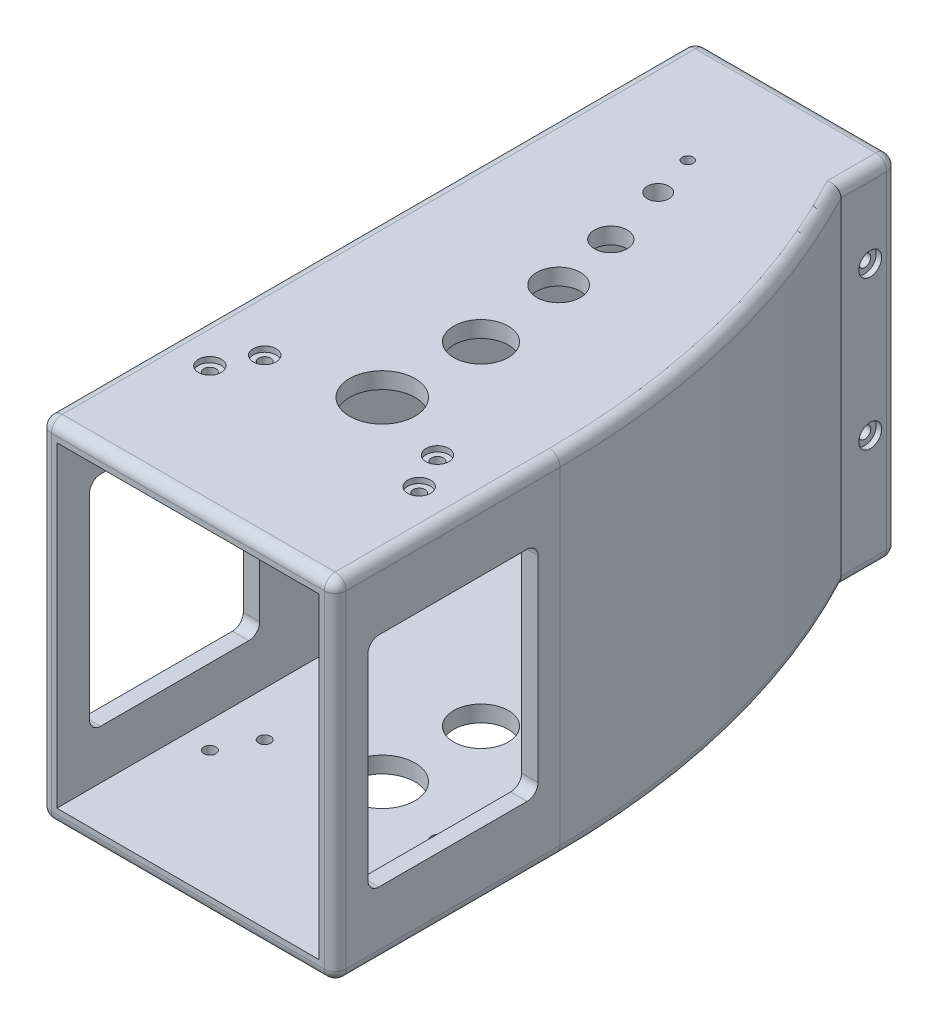
SolidWorks part; units mm, degrees
material "Custom Plastic"
ref_plane "Front Plane" through (0, 0, 0) normal (0, 0, 1) x (1, 0, 0)
ref_plane "Top Plane" through (0, 0, 0) normal (0, 1, 0) x (1, 0, 0)
ref_plane "Right Plane" through (0, 0, 0) normal (1, 0, 0) x (0, 0, -1)
sketch "Sketch3" plane through (0, 0, 0) normal (0, 1, 0) x (1, 0, 0)
  line L0 (0, 0) -> (54, 0)
  line L1 (54, 0) -> (54, 41.2013)
  line L2 (31, 120) -> (0, 120)
  line L3 (0, 120) -> (0, 0)
  arc A0 (54, 41.2013) -> (31, 120) centre (-92.4833, 41.2013) ccw
  dimension "D1" = 54
  dimension "D2" = 31
  dimension "D3" = 120
extrude "Boss-Extrude1" add sketch "Sketch3" along normal blind 64
sketch "Sketch5" plane through (0, 64, 0) normal (0, 1, 0) x (1, 0, 0)
  line L0 (31, 120) -> (37.0293, 120)
  line L1 (37.0293, 120) -> (37.0293, 109.64)
  arc A0 (54, 41.2013) -> (31, 120) centre (-92.4833, 41.2013) ccw construction
  arc A1 (31, 120) -> (37.0293, 109.64) centre (31, 113.0656) ccw
extrude "Boss-Extrude2" add sketch "Sketch5" against normal up to surface (64 mm away) up to face at (28.9265, 0, -56.5691)
shell "Shell1" thickness 3 removed face at (27, 32, 0)
fillet "Fillet1" radius 2 8 edges at (49.694, 0, -76.457) (49.694, 64, -76.457) (18.5146, 0, -120) (18.5146, 64, -120) (54, 0, -20.6007) (54, 64, -20.6007) (0, 0, -60) (0, 64, -60)
sketch "Sketch6" plane through (0, 0, -120) normal (0, 0, -1) x (-1, 0, 0)
  line L0 (0, 62) -> (-37.0293, 62) construction
  line L1 (-31.9074, 34) -> (-3, 34)
  line L2 (-31.9074, 34) -> (-31.9074, 59)
  line L3 (-31.9074, 59) -> (-3, 59)
  line L4 (-3, 34) -> (-3, 59)
  line L5 (-31.9074, 34) -> (-3, 59) construction
  line L6 (-31.9074, 59) -> (-3, 34) construction
  line L7 (0, 62) -> (0, 2) construction
  point P0 (-17.4537, 46.5)
  dimension "D1" = 3
  dimension "D2" = 3
  dimension "D3" = 25
extrude "Cut-Extrude1" cut sketch "Sketch6" against normal blind 64
sketch "Sketch8" plane through (37.0293, 0, 0) normal (1, 0, 0) x (0, 0, -1)
  line L0 (120, 2) -> (120, 62) construction
  circle A0 centre (115, 48.9095) radius 2.1
  circle A1 centre (115, 21.6579) radius 2.1
  point P6 (0, 0)
  point P7 (0, 0)
  dimension "D1" = 4.2
  dimension "D2" = 4.2
  dimension "D3" = 5
extrude "Cut-Extrude2" cut sketch "Sketch8" against normal blind 1
fillet "Fillet2" radius 2 13 edges at (0.5858, 63.4142, 0) (0, 32, 0) (0.5858, 0.5858, 0) (27, 0, 0) (53.4142, 0.5858, 0) (54, 32, 0) (53.4142, 63.4142, 0) (37.0293, 0, -111.6238) (37.0293, 0.5858, -119.4142) (37.0293, 32, -120) (37.0293, 63.4142, -119.4142) (27, 64, 0) (37.0293, 64, -111.6238)
fillet "Fillet3" radius 2 3 edges at (0.5858, 63.4142, -119.4142) (0.5858, 0.5858, -119.4142) (0, 32, -120)
fillet "Fillet4" radius 2 4 edges at (3, 34, -118.5) (31.9074, 34, -118.5) (31.9074, 59, -118.5) (3, 59, -118.5)
sketch "Sketch9" plane through (37.0293, 0, 0) normal (1, 0, 0) x (0, 0, -1)
  circle A0 centre (115, 48.9095) radius 1.1
  circle A1 centre (115, 21.6579) radius 1.1
  dimension "D1" = 2.2
  dimension "D2" = 2.2
extrude "Cut-Extrude3" cut sketch "Sketch9" against normal through all
sketch "Sketch10" plane through (0, 0, 0) normal (-1, 0, 0) x (0, 0, 1)
  circle A0 centre (-115, 48.9095) radius 2.1
  circle A1 centre (-115, 21.6579) radius 2.1
  dimension "D1" = 4.2
  dimension "D2" = 4.2
extrude "Cut-Extrude4" cut sketch "Sketch10" against normal blind 1
sketch "Sketch12" plane through (0, 64, 0) normal (0, 1, 0) x (1, 0, 0)
  line L0 (27, 2) -> (27, 41.1991) construction
  line L1 (2, 2) -> (52, 2) construction
  circle A0 centre (7.8252, 23.2099) radius 2.1
  circle A1 centre (11.172, 29.9036) radius 2.1
  dimension "D1" = 4.2
  dimension "D2" = 4.2
extrude "Cut-Extrude5" cut sketch "Sketch12" against normal blind 1
sketch "Sketch13" plane through (0, 64, 0) normal (0, 1, 0) x (1, 0, 0)
  circle A0 centre (7.8252, 23.2099) radius 1.1
  circle A1 centre (11.172, 29.9036) radius 1.1
  dimension "D1" = 2.2
  dimension "D2" = 2.2
extrude "Cut-Extrude6" cut sketch "Sketch13" against normal through all
sketch "Sketch14" plane through (0, 64, 0) normal (0, 1, 0) x (1, 0, 0)
  line L0 (27, 2) -> (27, 37.0116) construction
  line L1 (2, 2) -> (52, 2) construction
sketch "Sketch16" plane through (0, 0, -117) normal (0, 0, 1) x (1, 0, 0)
  line L0 (27, 62) -> (27, 14.4836) construction
  line L1 (52, 62) -> (2, 62) construction
ref_plane "Plane1" through (27, 0, 0) normal (-1, 0, 0) x (0, 0, 1)
mirror "Mirror1" about plane through (27, 0, 0) normal (-1, 0, 0) of "Cut-Extrude6", "Cut-Extrude5"
sketch "Sketch17" plane through (0, 0, -117) normal (0, 0, 1) x (1, 0, 0)
  line L0 (34.0293, 32) -> (56.7152, 32) construction
  line L1 (34.0293, 3) -> (34.0293, 61) construction
sketch "Sketch18" plane through (0, 0, 0) normal (0, -1, 0) x (1, 0, 0)
  circle A0 centre (7.8252, -23.2099) radius 2.1
  circle A1 centre (11.172, -29.9036) radius 2.1
  circle A2 centre (42.828, -29.9036) radius 2.1
  circle A3 centre (46.1748, -23.2099) radius 2.1
  dimension "D1" = 4.2
  dimension "D2" = 4.2
  dimension "D3" = 4.2
  dimension "D4" = 4.2
extrude "Cut-Extrude7" cut sketch "Sketch18" against normal blind 1
sketch "Sketch19" plane through (0, 0, 0) normal (-1, 0, 0) x (0, 0, 1)
  line L0 (-2, 32) -> (-118, 32) construction
  line L1 (-2, 2) -> (-2, 62) construction
  line L2 (-118, 62) -> (-118, 2) construction
  text T0 "                            SMART METHODS"
extrude "Cut-Extrude8" cut sketch "Sketch19" against normal blind 0.3
sketch "Sketch21" plane through (0, 64, 0) normal (0, 1, 0) x (1, 0, 0)
  line L0 (28.627, 33.9953) -> (31.2938, 61.488) construction
  line L1 (31.2938, 61.488) -> (18.9803, 99.6147) construction
  circle A0 centre (28.627, 33.9953) radius 6
  circle A1 centre (28.8537, 51.8609) radius 5
  circle A2 centre (26.9382, 67.9921) radius 4
  circle A3 centre (24.4898, 80.0045) radius 3
  circle A4 centre (21.3819, 91.7911) radius 2
  circle A5 centre (18.9803, 99.6147) radius 1
  spline S0 degree 2 poles (28.627, 33.9953) (31.2938, 61.488) (18.9803, 99.6147) knots 0 0 0 1 1 1
  point P13 (22.2451, 95.0241)
  point P14 (26.1873, 82.6345)
  point P15 (23.3715, 93.7101)
  point P16 (22.8083, 92.2083)
  point P17 (24.4978, 80.0064)
  point P18 (26.9382, 67.9921)
  dimension "D1" = 12
  dimension "D2" = 10
  dimension "D3" = 8
  dimension "D4" = 6
  dimension "D5" = 4
  dimension "D6" = 2
extrude "Cut-Extrude9" cut sketch "Sketch21" against normal through all and the other way blind 10 contours A0 | A1 | A2 | A3 | A4 | A5
sketch "Sketch22" plane through (54, 0, 0) normal (1, 0, 0) x (0, 0, -1)
  line L0 (2, 62) -> (2, 2) construction
  line L1 (6, 12) -> (37.1589, 12)
  line L2 (6, 12) -> (6, 52)
  line L3 (6, 52) -> (37.1589, 52)
  line L4 (37.1589, 12) -> (37.1589, 52)
  line L5 (6, 12) -> (37.1589, 52) construction
  line L6 (6, 52) -> (37.1589, 12) construction
  line L8 (41.2013, 62) -> (2, 62) construction
  line L10 (2, 2) -> (41.2013, 2) construction
  point P0 (21.5794, 32)
  dimension "D1" = 4
  dimension "D2" = 10
  dimension "D3" = 10
extrude "Cut-Extrude10" cut sketch "Sketch22" against normal through all
fillet "Fillet5" radius 2 8 edges at (1.5, 12, -37.1589) (1.5, 12, -6) (1.5, 52, -6) (1.5, 52, -37.1589) (52.5, 52, -37.1589) (52.5, 12, -37.1589) (52.5, 12, -6) (52.5, 52, -6)
